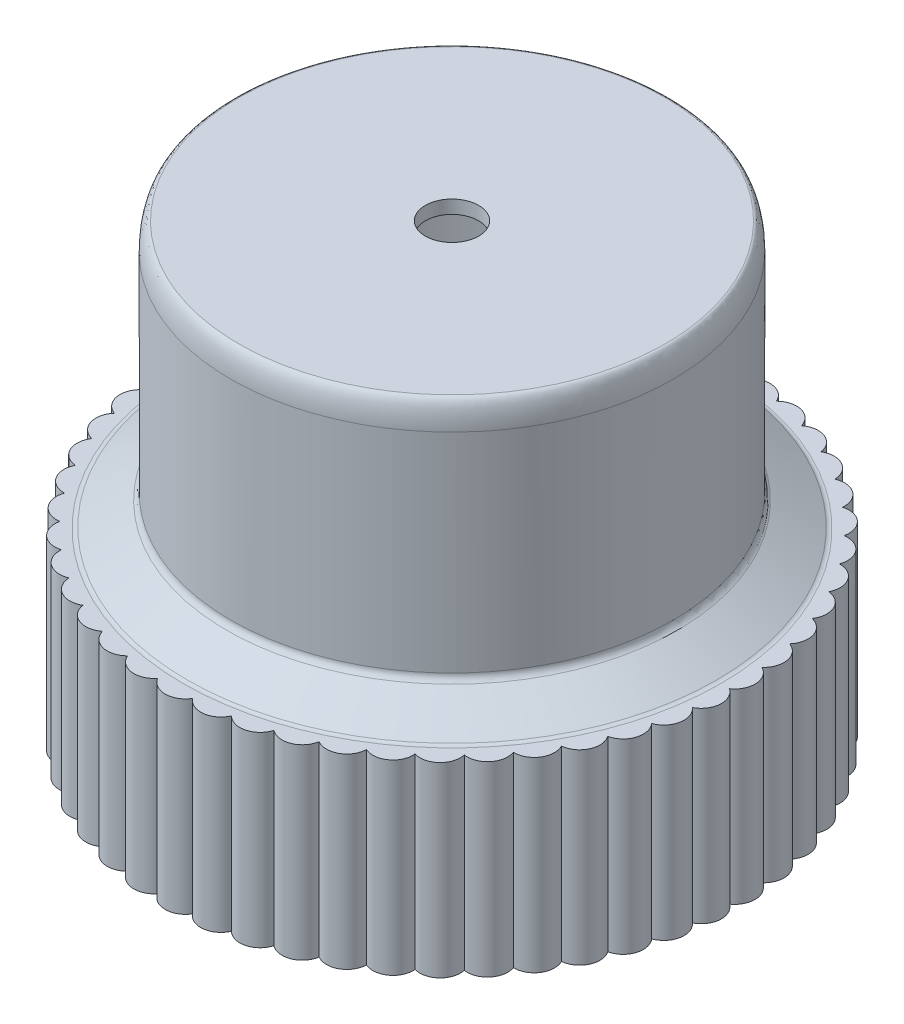
SolidWorks part; units mm, degrees
material "Brass"
ref_plane "Front Plane" through (0, 0, 0) normal (0, 0, 1) x (1, 0, 0)
ref_plane "Top Plane" through (0, 0, 0) normal (0, 1, 0) x (1, 0, 0)
ref_plane "Right Plane" through (0, 0, 0) normal (1, 0, 0) x (0, 0, -1)
sketch "Sketch1" plane through (0, 0, 0) normal (0, 0, 1) x (1, 0, 0)
  line L0 (0, 0) -> (0, 9.5) construction
  line L1 (5, 1) -> (5, 4.5)
  line L2 (5, 4.5) -> (4.15, 5)
  line L3 (4.15, 5) -> (4.15, 9.25)
  line L5 (4.15, 9.5) -> (0, 9.5)
  line L6 (0, 9.25) -> (3.9, 9.25)
  line L8 (3.9, 9.25) -> (3.9, 4.857)
  line L10 (4.75, 4.357) -> (4.75, 1.5)
  line L11 (4.75, 1.5) -> (5, 1)
  line L12 (0, 9.5) -> (0, 9.25)
  line L14 (4.15, 9.25) -> (4.15, 9.5)
  line L15 (3.9, 4.857) -> (4.75, 4.357)
  dimension "D1" = 3.5
  dimension "D2" = 0.5
  dimension "D3" = 0.25
  dimension "D4" = 0.5
  dimension "D5" = 0.25
  dimension "D6" = 0.25
  dimension "D7" = 0.25
  dimension "D8" = 4.15
  dimension "D9" = 4.5
  dimension "D10" = 5
  dimension "D11" = 9.5
revolve "Revolve1" add sketch "Sketch1" angle 360 about L0
fillet "Fillet1" radius 0.15 1 edges at (0, 9.5, -4.15) second distance 0.5 first distance on face at (0, 9.5, -4.15)
ref_plane "Plane1" through (0, 1, 0) normal (0, 1, 0) x (1, 0, 0)
sketch "Sketch3" plane through (0, 1, 0) normal (0, 1, 0) x (1, 0, 0)
  arc A0 (-0.3797, -4.9856) -> (0.3797, -4.9856) centre (0, -5) ccw
  circle A1 centre (0, 0) radius 5 construction
  arc A2 (-0.3797, -4.9856) -> (0.3797, -4.9856) centre (0, 0) ccw
  arc A3 (-0.3797, -4.9856) -> (0.3797, -4.9856) centre (0, 0) ccw
  dimension "D1" = 0.76
extrude "Boss-Extrude1" add sketch "Sketch3" along normal blind 3.5 contours A2 A0 region at (0, 1, 5.1586)
pattern_circular "CirPattern2" count 50 over 360 about axis through (0, 0, 0) along (0, -1, 0) of "Boss-Extrude1"
sketch "Sketch4" plane through (0, 9.5, 0) normal (0, 1, 0) x (1, 0, 0)
  circle A0 centre (0, 0) radius 0.5
  dimension "D1" = 1
extrude "Cut-Extrude1" cut sketch "Sketch4" against normal blind 3.5
fillet "Fillet2" radius 0.15 2 edges at (0, 4.5, -5) (0, 5, -4.15)
thread "Thread3" pitch 0.25 method extrude profile "Thread Profile3" start angle 1, offset 0, length 2.7, pitch 1, diameter 9.5
ref_plane "Plane6" through (4.7493, 1.5, -0.0829) normal (0.0175, 0, 0.9998) x (0.9998, 0, -0.0175)
sketch "Thread Profile3" plane through (4.7493, 1.5, -0.0829) normal (0.0175, 0, 0.9998) x (0.9998, 0, -0.0175)
  line L0 (0, 0) -> (0, 0.25) construction
  line L11 (0, 0) -> (0, 0.2187)
  line L12 (0, 0.2187) -> (-0.1353, 0.1406)
  line L13 (-0.1353, 0.1406) -> (-0.1353, 0.0781)
  line L15 (-0.1353, 0.0781) -> (0, 0)
  line L17 (-0.1353, 0.1094) -> (0, 0.1094) construction
  point P2 (0, 0)
  dimension "Pitch" = 0.25
  dimension "Profile_Angle" = 60
  dimension "Profile_Land" = 0.0625
  dimension "Profile_Height" = 0.1353
